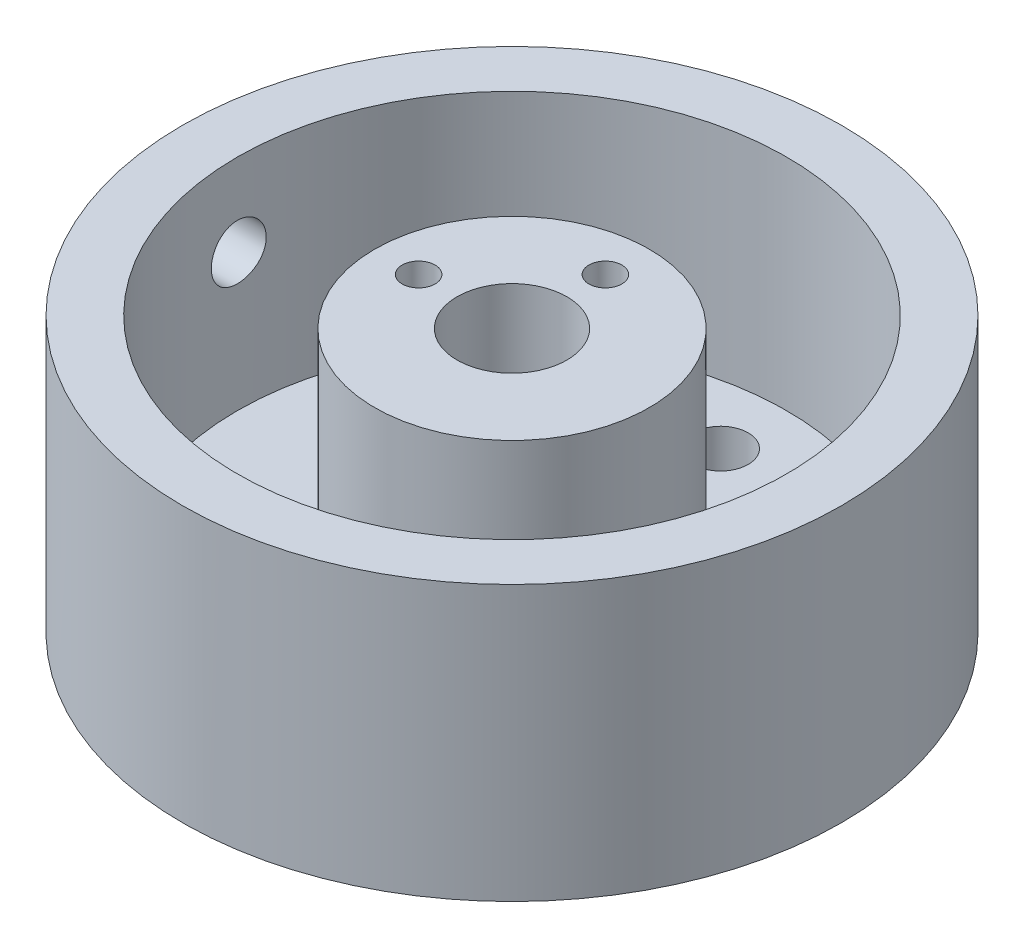
SolidWorks part; units mm, degrees
ref_plane "Front Plane" through (0, 0, 0) normal (0, 0, 1) x (1, 0, 0)
ref_plane "Top Plane" through (0, 0, 0) normal (0, 1, 0) x (1, 0, 0)
ref_plane "Right Plane" through (0, 0, 0) normal (1, 0, 0) x (0, 0, -1)
sketch "Sketch1" plane through (0, 0, 0) normal (0, 0, 1) x (1, 0, 0)
  line L0 (0, 23.98) -> (0, 0) construction
  line L1 (0, 0) -> (30, 0)
  line L2 (30, 0) -> (30, 25)
  line L3 (30, 25) -> (25, 25)
  line L4 (25, 25) -> (25, 5)
  line L5 (25, 5) -> (12.5, 5)
  line L6 (12.5, 5) -> (12.5, 23.98)
  line L7 (12.5, 23.98) -> (0, 23.98)
  line L8 (5, 23.98) -> (5, 0)
  line L9 (5, 11.48) -> (7, 11.48)
  line L10 (7, 11.48) -> (7, 7.28)
  line L11 (7, 7.28) -> (5, 7.28)
  dimension "D1" = 30
  dimension "D2" = 25
  dimension "D3" = 5
  dimension "D4" = 5
  dimension "D5" = 23.98
  dimension "D6" = 12.5
  dimension "D7" = 5
  dimension "D8" = 2
  dimension "D9" = 4.2
  dimension "D10" = 12.5
revolve "Revolve2" add sketch "Sketch1" angle 360 about L0 region at (5.3536, 3.64, 0)
sketch "Sketch2" plane through (0, 0, 0) normal (0, -1, 0) x (1, 0, 0)
  circle A0 centre (0, -19) radius 2.5
  dimension "D1" = 19
  dimension "D3" = 5
extrude "Cut-Extrude1" cut sketch "Sketch2" against normal blind 10
sketch "Sketch3" plane through (0, 23.98, 0) normal (0, 1, 0) x (1, 0, 0)
  circle A0 centre (-8.5, 0) radius 1.5
  circle A1 centre (0, 8.5) radius 1.5
  dimension "D1" = 3
  dimension "D2" = 8.5
  dimension "D3" = 8.5
extrude "Cut-Extrude2" cut sketch "Sketch3" against normal blind 8
ref_plane "Plane1" through (0, 0, -12.5) normal (0, 0, 1) x (1, 0, 0)
sketch "Sketch4" plane through (0, 0, -12.5) normal (0, 0, 1) x (1, 0, 0)
  line L0 (12.5, 23.98) -> (-12.5, 23.98) construction
  circle A0 centre (0, 17.5) radius 1.5
  dimension "D1" = 3
  dimension "D2" = 6.48
extrude "Cut-Extrude3" cut sketch "Sketch4" along normal blind 4
ref_plane "Plane2" through (-12.5, 0, 0) normal (1, 0, 0) x (0, 0, -1)
sketch "Sketch5" plane through (-12.5, 0, 0) normal (1, 0, 0) x (0, 0, -1)
  line L0 (5, 23.98) -> (-5, 23.98) construction
  circle A0 centre (0, 17.5) radius 1.5
  dimension "D1" = 6.48
  dimension "D2" = 3
extrude "Cut-Extrude4" cut sketch "Sketch5" along normal blind 4
ref_plane "Plane3" through (-30, 0, 0) normal (1, 0, 0) x (0, 0, -1)
sketch "Sketch6" plane through (-30, 0, 0) normal (1, 0, 0) x (0, 0, -1)
  circle A0 centre (0, 17.5) radius 2.5
  dimension "D1" = 5
extrude "Cut-Extrude7" cut sketch "Sketch6" along normal blind 10 and the other way blind 10
sketch "Sketch7" plane through (0, 0, 0) normal (0, 0, 1) x (1, 0, 0)
  line L0 (-32, 0) -> (-30, 0)
  line L1 (-30, 0) -> (30, 0) construction
  line L2 (-30, 0) -> (-15, 0)
  line L3 (-5, 0) -> (5, 0) construction
  line L4 (-15, 0) -> (-15, -9.5)
  line L5 (-18, -12.5) -> (-32, -12.5)
  line L6 (-35, -9.5) -> (-35, -3)
  circle A0 centre (-25, -7.5) radius 2.5
  arc A1 (-15, -9.5) -> (-18, -12.5) centre (-18, -9.5) cw
  arc A2 (-32, -12.5) -> (-35, -9.5) centre (-32, -9.5) cw
  arc A3 (-35, -3) -> (-32, 0) centre (-32, -3) cw
  point P3 (-15, -12.5)
  dimension "D1" = 30
  dimension "D3" = 5
  dimension "D8" = 3
  dimension "D2" = 25
  dimension "D4" = 7.5
  dimension "D5" = 12.5
  dimension "D6" = 10
  dimension "D7" = 10
extrude "Boss-Extrude5" add sketch "Sketch7" along normal blind 5 and the other way blind 5
